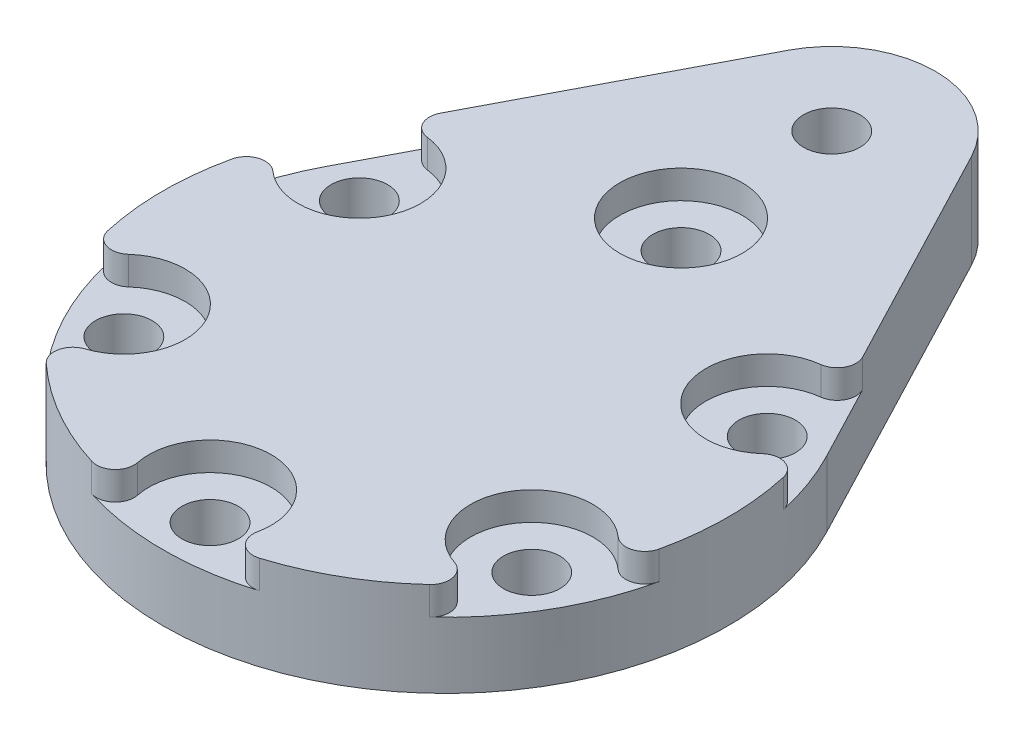
SolidWorks part; units mm, degrees
ref_plane "Front Plane" through (0, 0, 0) normal (0, 0, 1) x (1, 0, 0)
ref_plane "Top Plane" through (0, 0, 0) normal (0, 1, 0) x (1, 0, 0)
ref_plane "Right Plane" through (0, 0, 0) normal (1, 0, 0) x (0, 0, -1)
sketch "Sketch4" plane through (0, 0, 0) normal (0, 1, 0) x (1, 0, 0)
  line L0 (0, 0) -> (0, 20.5) construction
  line L1 (-4.8738, 23.0488) -> (-13.2921, 6.9512)
  line L2 (4.8738, 23.0488) -> (13.2921, 6.9512)
  circle A0 centre (0, 0) radius 12.5 construction
  circle A1 centre (0, 0) radius 15
  circle A2 centre (0, 12.5) radius 1.5
  circle A3 centre (10.8253, 6.25) radius 1.5
  circle A4 centre (10.8253, -6.25) radius 1.5
  circle A5 centre (0, -12.5) radius 1.5
  circle A6 centre (-10.8253, -6.25) radius 1.5
  circle A7 centre (-10.8253, 6.25) radius 1.5
  circle A8 centre (0, 20.5) radius 1.5
  circle A9 centre (0, 20.5) radius 5.5
  point P18 (0, 0)
  dimension "D1" = 25
  dimension "D2" = 30
  dimension "D3" = 3
  dimension "D6" = 3
  dimension "D5" = 20.5
  dimension "D4" = 6
extrude "Boss-Extrude1" add sketch "Sketch4" along normal blind 5 contours A9 A8 | A9 L1 A1 | A9 A1 L2 | A1 A7 A6 A5 A4 A3 A2 region at (-6.7798, 0, -15.4196) region at (0, 0, -25.8444) region at (0, 0, 0) region at (6.7798, 0, -15.4196)
sketch "Sketch6" plane through (0, 5, 0) normal (0, 1, 0) x (1, 0, 0)
  circle A0 centre (0, 0) radius 12.5 construction
  circle A1 centre (0, 12.5) radius 3.25
  circle A2 centre (10.8253, 6.25) radius 3.25
  circle A3 centre (10.8253, -6.25) radius 3.25
  circle A4 centre (0, -12.5) radius 3.25
  circle A5 centre (-10.8253, -6.25) radius 3.25
  circle A6 centre (-10.8253, 6.25) radius 3.25
  point P19 (0, 0)
  dimension "D1" = 6.5
  dimension "D2" = 6
extrude "Cut-Extrude1" cut sketch "Sketch6" against normal blind 1.5
fillet "Fillet1" radius 1 10 edges at (-12.0941, 4.25, -9.2421) (-13.9751, 4.25, -5.4493) (-11.7068, 4.25, 9.3782) (-13.9751, 4.25, 5.4493) (-2.2683, 4.25, 14.8275) (2.2683, 4.25, 14.8275) (11.7068, 4.25, 9.3782) (13.9751, 4.25, 5.4493) (13.9751, 4.25, -5.4493) (12.0941, 4.25, -9.2421)
